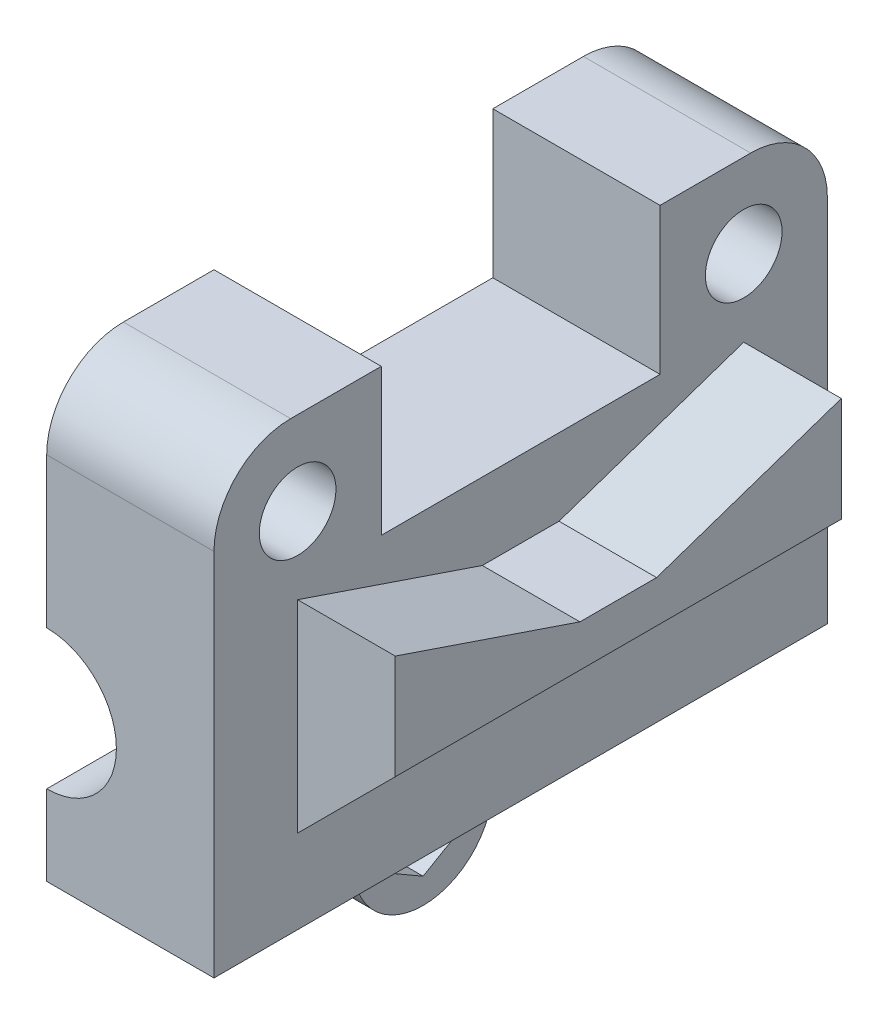
SolidWorks part; units mm, degrees
ref_plane "Front Plane" through (0, 0, 0) normal (0, 0, 1) x (1, 0, 0)
ref_plane "Top Plane" through (0, 0, 0) normal (0, 1, 0) x (1, 0, 0)
ref_plane "Right Plane" through (0, 0, 0) normal (1, 0, 0) x (0, 0, -1)
sketch "Sketch1" plane through (0, 0, 0) normal (1, 0, 0) x (0, 0, -1)
  line L1 (-22, -16) -> (22, -16)
  line L2 (-22, -16) -> (-22, 16)
  line L3 (-22, 16) -> (22, 16)
  line L4 (22, -16) -> (22, 16)
  line L5 (-22, -16) -> (22, 16) construction
  line L6 (-22, 16) -> (22, -16) construction
  point P0 (0, 0)
  dimension "D1" = 44
  dimension "D2" = 32
extrude "Boss-Extrude1" add sketch "Sketch1" along normal blind 12
sketch "Sketch2" plane through (0, 0, 0) normal (1, 0, 0) x (0, 0, -1)
  line L0 (-22, -16) -> (22, -16) construction
  line L1 (12.25, -13) -> (-12.25, -13)
  line L2 (12.25, -13) -> (12.25, 2.5)
  line L3 (12.25, 2.5) -> (-12.25, 2.5)
  line L4 (-12.25, -13) -> (-12.25, 2.5)
  line L5 (12.25, -13) -> (-12.25, 2.5) construction
  line L6 (12.25, 2.5) -> (-12.25, -13) construction
  point P0 (0, -5.25)
  dimension "D1" = 24.5
  dimension "D2" = 15.5
  dimension "D3" = 0
  dimension "D4" = 3
extrude "Cut-Extrude1" cut sketch "Sketch2" along normal blind 7.75 contours L2 L1 L4 L3
fillet "Fillet1" radius 7.75 2 edges at (7.75, 2.5, 0) (7.75, -13, 0)
sketch "Sketch3" plane through (0, 0, -12.25) normal (0, 0, 1) x (1, 0, 0)
  arc A0 (0, -13) -> (7.75, -5.25) centre (0, -5.25) ccw construction
  arc A1 (0, -13) -> (7.75, -5.25) centre (0, -5.25) ccw
  circle A2 centre (0, -5.25) radius 5
  line M3 (0, 2.5) -> (0, -13)
  dimension "D1" = 10
extrude "Cut-Extrude2" cut sketch "Sketch3" against normal through all both and the other way through all contours A2 M3 | A2 M3 region at (2.1221, -5.25, -12.25) region at (-2.1221, -5.25, -12.25)
sketch "Sketch4" plane through (12, 0, 0) normal (1, 0, 0) x (0, 0, -1)
  line L0 (22, 16) -> (-22, 16) construction
  line L2 (-10, 16) -> (10, 16)
  line L3 (-10, 16) -> (-10, 5.5)
  line L4 (-10, 5.5) -> (10, 5.5)
  line L5 (10, 16) -> (10, 5.5)
  circle A0 centre (-16, 10) radius 2.75
  circle A1 centre (16, 10) radius 2.75
  dimension "D1" = 5.5
  dimension "D2" = 5.5
  dimension "D3" = 6
  dimension "D4" = 6
  dimension "D5" = 6
  dimension "D6" = 6
  dimension "D7" = 32
  dimension "D8" = 10
  dimension "D9" = 10.5
extrude "Cut-Extrude3" cut sketch "Sketch4" against normal through all
sketch "Sketch5" plane through (12, 0, 0) normal (1, 0, 0) x (0, 0, -1)
  line L0 (-16, 10) -> (-16, 4.5)
  line L1 (-2.75, -3) -> (2.75, -3)
  line L2 (-2.75, -3) -> (-2.75, 0)
  line L3 (-2.75, 0) -> (2.75, 0)
  line L4 (2.75, -3) -> (2.75, 0)
  line L5 (-2.75, -3) -> (2.75, 0) construction
  line L6 (-2.75, 0) -> (2.75, -3) construction
  line L7 (16, 10) -> (16, 4.5)
  line L8 (-2.75, 0) -> (-16, 4.5)
  line L9 (2.75, 0) -> (16, 4.5)
  line L10 (2.75, -3) -> (16, 4.5)
  line L11 (-2.75, -3) -> (-16, 4.5)
  line L12 (16, 4.5) -> (16, -3)
  line L13 (16, -3) -> (2.75, -3)
  line L14 (-2.75, -3) -> (-16, -3)
  line L15 (-16, -3) -> (-16, 4.5)
  circle A0 centre (16, 10) radius 2.75 construction
  circle A1 centre (16, 10) radius 2.75
  circle A2 centre (-16, 10) radius 2.75 construction
  circle A3 centre (-16, 10) radius 2.75
  point P0 (0, -1.5)
  dimension "D1" = 10
  dimension "D2" = 3
  dimension "D3" = 5.5
  dimension "D4" = 0
  dimension "D5" = 5.5
  dimension "D6" = 5.5
extrude "Boss-Extrude4" add sketch "Sketch5" along normal blind 7 contours L15 L14 L11 | L11 L2 L8 | L1 L4 L3 L2 | L4 L10 L9 | L13 L12 L10 region at (12, 0.5, 7.1667) region at (12, -0.5, 11.5833) region at (12, -1.5, 0) region at (12, 0.5, -7.1667) region at (12, -0.5, -11.5833)
chamfer "Chamfer1" distance 7 angle 45 1 edges at (12, -3, 0)
sketch "Sketch6" plane through (12, 0, 0) normal (1, 0, 0) x (0, 0, -1)
  line L0 (16, -3) -> (-16, -3) construction
  line L1 (16, -3) -> (-16, -3)
  line L2 (16, -10) -> (-16, -10) construction
  line L3 (-13, -3) -> (13, -3)
  line L4 (-13, -3) -> (-13, -10)
  line L5 (-13, -10) -> (13, -10)
  line L6 (13, -3) -> (13, -10)
  line L7 (-16, -10) -> (-16, -3) construction
  line L8 (10, 5.5) -> (-10, 5.5)
  line L9 (-10, 5.5) -> (-10, 16)
  line L10 (-10, 16) -> (-22, 16)
  line L11 (-22, 16) -> (-22, -16)
  line L12 (-22, -16) -> (22, -16)
  line L13 (22, -16) -> (22, 16)
  line L14 (22, 16) -> (10, 16)
  line L15 (10, 16) -> (10, 5.5)
  line L16 (10, 5.5) -> (-10, 5.5)
  line L17 (-10, 5.5) -> (-10, 16)
  line L18 (-10, 16) -> (-22, 16)
  line L19 (-22, 16) -> (-22, -16)
  line L20 (-22, -16) -> (22, -16)
  line L21 (22, -16) -> (22, 16)
  line L22 (22, 16) -> (10, 16)
  line L23 (10, 16) -> (10, 5.5)
  line L24 (16, 4.5) -> (16, -10) construction
  line L25 (-2.75, 0) -> (2.75, 0) construction
  line L26 (-1.5, -3) -> (1.5, -3)
  line L27 (-1.5, -3) -> (-1.5, -10)
  line L28 (-1.5, -10) -> (1.5, -10)
  line L29 (1.5, -3) -> (1.5, -10)
  point P26 (0, 0)
  line M13 (16, -10) -> (-16, -10)
  dimension "D2" = 3
  dimension "D3" = 3
  dimension "D4" = 3
  dimension "D5" = 1.5
  dimension "D1" = 0
extrude "Cut-Extrude5" cut sketch "Sketch6" along normal through all contours L27 L1 L4 L5 | L1 L29 L6 M13 region at (12, -6.5, -7.25) region at (12, -6.5, 7.25)
fillet "Fillet4" radius 5.5 2 edges at (6, 16, -22) (6, 16, 22)
sketch "Sketch7" plane through (0, 0, 0) normal (1, 0, 0) x (0, 0, -1)
  line L0 (-22, -16) -> (22, -16) construction
  line L1 (5, -16) -> (-5, -16)
  line L2 (5, -16) -> (5, -26)
  line L3 (5, -26) -> (-5, -26)
  line L4 (-5, -16) -> (-5, -26)
  circle A0 centre (0, -21) radius 2
  dimension "D4" = 4
  dimension "D1" = 10
  dimension "D2" = 10
  dimension "D3" = 5
  dimension "D5" = 5
extrude "Boss-Extrude5" add sketch "Sketch7" along normal blind 5
sketch "Sketch8" plane through (5, 0, 0) normal (1, 0, 0) x (0, 0, -1)
  line L1 (0, -24.1754) -> (2.75, -22.5877)
  line L2 (2.75, -22.5877) -> (2.75, -19.4123)
  line L3 (2.75, -19.4123) -> (0, -17.8246)
  line L4 (0, -17.8246) -> (-2.75, -19.4123)
  line L5 (-2.75, -19.4123) -> (-2.75, -22.5877)
  line L6 (-2.75, -22.5877) -> (0, -24.1754)
  circle A0 centre (0, -21) radius 2 construction
  circle A1 centre (0, -21) radius 2
  circle A2 centre (0, -21) radius 2.75 construction
  dimension "D1" = 5.5
extrude "Cut-Extrude6" cut sketch "Sketch8" against normal blind 2
fillet "Fillet5" radius 5 2 edges at (2.5, -26, -5) (2.5, -26, 5)
sketch "Sketch9" plane through (0, 0, 0) normal (-1, 0, 0) x (0, 0, 1)
  line L1 (-16, 5.3812) -> (-12, 7.6906)
  line L2 (-12, 7.6906) -> (-12, 12.3094)
  line L3 (-12, 12.3094) -> (-16, 14.6188)
  line L4 (-16, 14.6188) -> (-20, 12.3094)
  line L5 (-20, 12.3094) -> (-20, 7.6906)
  line L6 (-20, 7.6906) -> (-16, 5.3812)
  line L7 (16, 5.3812) -> (20, 7.6906)
  line L8 (20, 7.6906) -> (20, 12.3094)
  line L9 (20, 12.3094) -> (16, 14.6188)
  line L10 (16, 14.6188) -> (12, 12.3094)
  line L11 (12, 12.3094) -> (12, 7.6906)
  line L12 (12, 7.6906) -> (16, 5.3812)
  circle A0 centre (16, 10) radius 2.75 construction
  circle A1 centre (-16, 10) radius 2.75 construction
  circle A2 centre (16, 10) radius 2.75
  circle A3 centre (-16, 10) radius 2.75
  circle A4 centre (-16, 10) radius 4 construction
  circle A5 centre (16, 10) radius 4 construction
  point P6 (20, 10)
  dimension "D1" = 8
  dimension "D2" = 8
extrude "Cut-Extrude7" cut sketch "Sketch9" against normal blind 4
